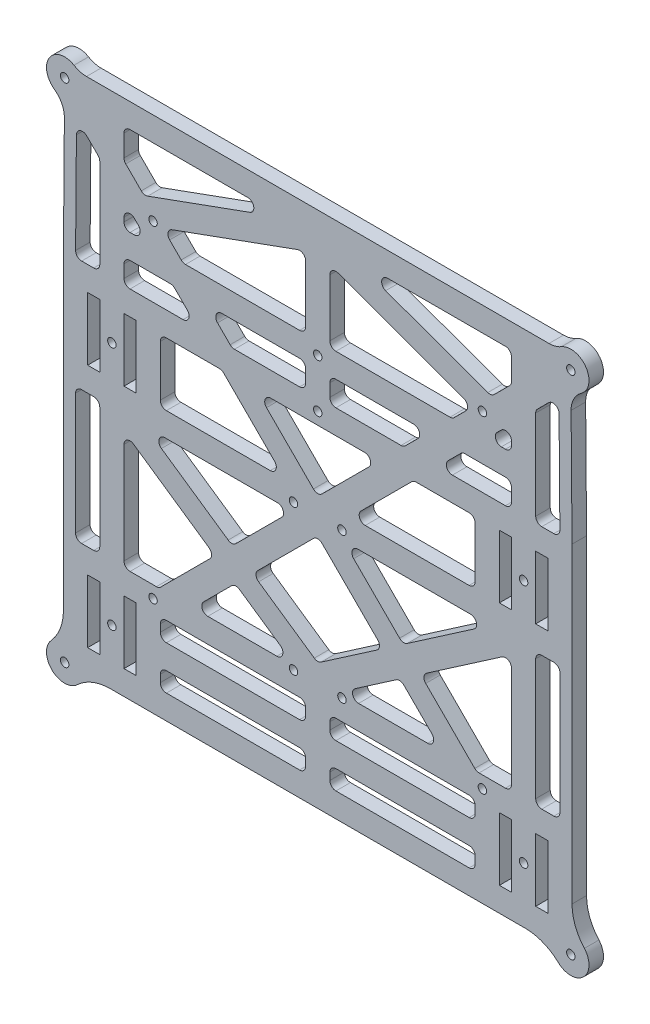
SolidWorks part; units mm, degrees
material "PMMA"
ref_plane "Płaszczyzna przednia" through (0, 0, 0) normal (0, 0, 1) x (1, 0, 0)
ref_plane "Płaszczyzna górna" through (0, 0, 0) normal (0, 1, 0) x (1, 0, 0)
ref_plane "Płaszczyzna prawa" through (0, 0, 0) normal (1, 0, 0) x (0, 0, -1)
sketch "Szkic1" plane through (0, 0, 0) normal (0, 0, 1) x (1, 0, 0)
  line L0 (-85, 104.5) -> (-85, -104.5)
  line L1 (-104.5, -104.5) -> (104.5, -104.5) construction
  line L2 (-104.5, -104.5) -> (-104.5, 104.5) construction
  line L3 (-104.5, 104.5) -> (104.5, 104.5) construction
  line L4 (104.5, -104.5) -> (104.5, 104.5) construction
  line L5 (0, 104.5) -> (0, -104.5) construction
  line L6 (-104.5, 0) -> (104.5, 0) construction
  line L7 (85, -104.5) -> (85, 104.5)
  circle A0 centre (104.5, 104.5) radius 1.75
  circle A1 centre (-104.5, 104.5) radius 1.75
  circle A2 centre (-104.5, -104.5) radius 1.75
  circle A3 centre (104.5, -104.5) radius 1.75
  point P0 (0, 0)
  dimension "D2" = 3.5
  dimension "D1" = 209
  dimension "D3" = 170
sketch "Szkic3" plane through (0, 0, 0) normal (0, 0, 1) x (1, 0, 0)
  line L6 (-80, 104.5) -> (-80, -104.5)
  line L7 (-80, -104.5) -> (-90, -104.5)
  line L8 (-90, -104.5) -> (-90, 104.5)
  line L9 (-90, 104.5) -> (-80, 104.5)
  line L10 (80, 104.5) -> (90, 104.5)
  line L11 (90, 104.5) -> (90, -104.5)
  line L12 (90, -104.5) -> (80, -104.5)
  line L13 (80, -104.5) -> (80, 104.5)
  line L15 (85, -104.5) -> (85, 104.5) construction
  line L16 (-85, 104.5) -> (-85, -104.5) construction
  dimension "D1" = 10
  dimension "D2" = 10
extrude "Dodanie-wyciągnięcie1" add sketch "Szkic3" along normal blind 6
sketch "Szkic4" plane through (0, 0, 0) normal (0, 0, 1) x (1, 0, 0)
  line L0 (-95, -94.5) -> (95, -94.5)
  line L3 (-95, -94.5) -> (-95, -104.5)
  line L4 (-95, -104.5) -> (95, -104.5)
  line L5 (95, -104.5) -> (95, -94.5)
  line L6 (-95, -68.5) -> (95, -68.5)
  line L7 (95, -68.5) -> (95, -58.5)
  line L8 (95, -58.5) -> (-95, -58.5)
  line L9 (-95, -58.5) -> (-95, -68.5)
  line L10 (-104.5, -31) -> (104.5, -31) construction
  line L12 (-95, -3.5) -> (-95, 6.5)
  line L13 (95, -3.5) -> (-95, -3.5)
  line L14 (95, 6.5) -> (95, -3.5)
  line L15 (-95, 6.5) -> (95, 6.5)
  line L16 (95, 42.5) -> (95, 32.5)
  line L17 (-95, 42.5) -> (95, 42.5)
  line L18 (-95, 32.5) -> (-95, 42.5)
  line L19 (-95, 32.5) -> (95, 32.5)
  line L20 (104.5, -104.5) -> (104.5, 104.5) construction
  line L21 (-104.5, -104.5) -> (-104.5, 104.5) construction
  line L23 (-90, -104.5) -> (-80, -104.5) construction
  line L24 (-90, 104.5) -> (-90, -104.5) construction
  line L25 (0, -31) -> (0, -14.952) construction
  line L26 (0, 104.5) -> (0, -104.5) construction
  dimension "D1" = 10
  dimension "D2" = 26
  dimension "D3" = 5
  dimension "D4" = 27.5
extrude "Dodanie-wyciągnięcie2" add sketch "Szkic4" along normal blind 6
sketch "Szkic5" plane through (0, 0, 6) normal (0, 0, 1) x (1, 0, 0)
  line L0 (-75, -68.5) -> (-75, -94.5)
  line L8 (-80, -68.5) -> (80, -68.5) construction
  line L9 (80, -94.5) -> (-80, -94.5) construction
  line L10 (-75, -94.5) -> (-65, -94.5)
  line L11 (-65, -94.5) -> (-65, -68.5)
  line L12 (-65, -68.5) -> (-75, -68.5)
  line L14 (-85, 104.5) -> (-85, -104.5) construction
  line L15 (-75, 32.5) -> (-75, 6.5)
  line L16 (-80, 32.5) -> (80, 32.5) construction
  line L17 (80, 6.5) -> (-80, 6.5) construction
  line L18 (-75, 6.5) -> (-65, 6.5)
  line L19 (-65, 6.5) -> (-65, 32.5)
  line L20 (-65, 32.5) -> (-75, 32.5)
  line L21 (0, 104.5) -> (0, -104.5) construction
  line L22 (65, 32.5) -> (75, 32.5)
  line L23 (65, 6.5) -> (65, 32.5)
  line L24 (75, 6.5) -> (65, 6.5)
  line L25 (75, 32.5) -> (75, 6.5)
  line L26 (65, -68.5) -> (75, -68.5)
  line L27 (65, -94.5) -> (65, -68.5)
  line L28 (75, -94.5) -> (65, -94.5)
  line L29 (75, -68.5) -> (75, -94.5)
  dimension "D1" = 10
  dimension "D2" = 10
extrude "Dodanie-wyciągnięcie3" add sketch "Szkic5" against normal blind 6
sketch "Szkic6" plane through (0, 0, 0) normal (0, 0, 1) x (1, 0, 0)
  line L1 (-95, 42.5) -> (-105, 42.5)
  line L2 (-95, 42.5) -> (-95, -3.5)
  line L3 (-95, -3.5) -> (-105, -3.5)
  line L4 (-105, 42.5) -> (-105, -3.5)
  line L5 (-95, -58.5) -> (-105, -58.5)
  line L6 (-95, -58.5) -> (-95, -104.5)
  line L7 (-95, -104.5) -> (-105, -104.5)
  line L8 (-105, -58.5) -> (-105, -104.5)
  line L9 (0, 104.5) -> (0, -104.5) construction
  line L10 (-104.5, 104.5) -> (104.5, 104.5) construction
  line L11 (105, -58.5) -> (105, -104.5)
  line L12 (95, -104.5) -> (105, -104.5)
  line L13 (95, -58.5) -> (95, -104.5)
  line L14 (95, -58.5) -> (105, -58.5)
  line L15 (105, 42.5) -> (105, -3.5)
  line L16 (95, -3.5) -> (105, -3.5)
  line L17 (95, 42.5) -> (95, -3.5)
  line L18 (95, 42.5) -> (105, 42.5)
  dimension "D1" = 10
extrude "Dodanie-wyciągnięcie4" add sketch "Szkic6" along normal up to surface (6 mm away) up to face at (0, -81.5, 6)
sketch "Szkic7" plane through (0, 0, 6) normal (0, 0, 1) x (1, 0, 0)
  line L0 (-104.5, -104.5) -> (104.5, -104.5) construction
  circle A0 centre (-104.5, -104.5) radius 7.5
  circle A1 centre (104.5, -104.5) radius 7.5
  dimension "D1" = 15
extrude "Dodanie-wyciągnięcie5" add sketch "Szkic7" against normal up to surface (6 mm away) contours A0 | A1 region at (-104.5, -104.5, 6) up to face at (92.5, 19.5, 0)
fillet "Zaokrąglenie1" radius 20 4 edges at (105, -97.0167, 3) (97, -104.5, 3) (-97, -104.5, 3) (-105, -97.0167, 3)
sketch "Szkic8" plane through (0, 0, 6) normal (0, 0, 1) x (1, 0, 0)
  circle A0 centre (-104.5, 104.5) radius 7.5
  circle A1 centre (104.5, 104.5) radius 7.5
  arc A2 (-110.0909, -99.5008) -> (-99.3524, -109.9545) centre (-104.5, -104.5) ccw construction
extrude "Dodanie-wyciągnięcie6" add sketch "Szkic8" against normal up to surface (6 mm away) separate body up to face at (0, -14.7636, 0)
sketch "Szkic9" plane through (0, 0, 0) normal (0, 0, 1) x (1, 0, 0)
  line L0 (-104.5, 104.5) -> (104.5, 104.5) construction
  line L1 (-104.5, 99.5) -> (104.5, 99.5)
  line L2 (-104.5, 109.5) -> (104.5, 109.5)
  line L3 (-104.5, 99.5) -> (-104.5, 109.5)
  line L4 (104.5, 99.5) -> (104.5, 109.5)
  dimension "D1" = 5
  dimension "D2" = 5
extrude "Dodanie-wyciągnięcie7" add sketch "Szkic9" along normal up to surface (6 mm away) up to face at (0, -14.7636, 6)
sketch "Szkic10" plane through (0, 0, 0) normal (0, 0, 1) x (1, 0, 0)
  line L0 (-104.5, 104.5) -> (104.5, -104.5) construction
  line L1 (104.5, 104.5) -> (-104.5, -104.5) construction
  line L2 (-80, -58.5) -> (80, -58.5) construction
  line L3 (-108.0355, 100.9645) -> (51.4289, -58.5)
  line L4 (100.9645, 108.0355) -> (-65.5711, -58.5)
  line L5 (-100.9645, 108.0355) -> (65.5711, -58.5)
  line L6 (108.0355, 100.9645) -> (-51.4289, -58.5)
  line L7 (100.9645, 108.0355) -> (-108.0355, -100.9645) construction
  line L8 (108.0355, 100.9645) -> (-100.9645, -108.0355) construction
  line L9 (-108.0355, 100.9645) -> (100.9645, -108.0355) construction
  line L10 (-100.9645, 108.0355) -> (108.0355, -100.9645) construction
  line L11 (-65.5711, -58.5) -> (-51.4289, -58.5)
  line L12 (65.5711, -58.5) -> (51.4289, -58.5)
  line L13 (-100.9645, 108.0355) -> (-108.0355, 100.9645)
  line L14 (100.9645, 108.0355) -> (108.0355, 100.9645)
  dimension "D1" = 5
  dimension "D2" = 5
extrude "Dodanie-wyciągnięcie8" add sketch "Szkic10" along normal up to surface (6 mm away) contours L5 L13 L3 L4 | L14 L4 L5 L6 | L4 L11 L6 L3 | L6 L5 L4 L3 | L12 L5 L6 L3 region at (-54.0178, 54.0178, 0) region at (0, 0, 0) region at (-31.1315, -30.9799, 0) region at (31.1315, -30.9799, 0) region at (54.0178, 54.0178, 0) up to face at (0, -10.379, 6)
sketch "Szkic11" plane through (0, 0, 0) normal (0, 0, -1) x (-1, 0, 0)
  line L0 (-65, -81.5) -> (65, -81.5) construction
  line L1 (-65, -68.5) -> (-65, -94.5) construction
  line L2 (65, -94.5) -> (65, -68.5) construction
  line L3 (80, 57.7145) -> (-80, 57.7145) construction
  line L4 (80, 42.5) -> (80, 72.9289) construction
  line L5 (-80, 72.9289) -> (-80, 42.5) construction
  line L6 (80, 62.7145) -> (-80, 62.7145)
  line L7 (80, 52.7145) -> (-80, 52.7145)
  line L8 (80, 62.7145) -> (80, 52.7145)
  line L9 (-80, 62.7145) -> (-80, 52.7145)
  line L10 (-65, -86.5) -> (65, -86.5)
  line L11 (-65, -76.5) -> (65, -76.5)
  line L12 (-65, -86.5) -> (-65, -76.5)
  line L13 (65, -86.5) -> (65, -76.5)
  dimension "D1" = 5
  dimension "D2" = 5
  dimension "D3" = 5
  dimension "D4" = 5
extrude "Dodanie-wyciągnięcie9" add sketch "Szkic11" against normal up to surface (6 mm away) up to face at (-90.8096, 98.6904, 6)
sketch "Szkic12" plane through (0, 0, 0) normal (0, 0, -1) x (-1, 0, 0)
  line L0 (-80, -3.5) -> (0, -58.5) construction
  line L1 (-51.4289, -58.5) -> (51.4289, -58.5) construction
  line L2 (0, -58.5) -> (80, -3.5) construction
  line L3 (-82.8326, -7.6202) -> (0, -64.5677)
  line L4 (0, -64.5677) -> (82.8326, -7.6202)
  line L5 (-77.1674, 0.6202) -> (0, -52.4323)
  line L6 (0, -52.4323) -> (77.1674, 0.6202)
  line L7 (-82.8326, -7.6202) -> (-77.1674, 0.6202)
  line L8 (82.8326, -7.6202) -> (77.1674, 0.6202)
  dimension "D1" = 5
  dimension "D2" = 5
extrude "Dodanie-wyciągnięcie10" add sketch "Szkic12" against normal up to surface (6 mm away) up to face at (0, -90.5, 6)
sketch "Szkic13" plane through (0, 0, 0) normal (0, 0, -1) x (-1, 0, 0)
  line L0 (-67.8217, 74.8928) -> (0, 99.5) construction
  line L1 (-80, 87.0711) -> (-55.6434, 62.7145) construction
  line L2 (80, 99.5) -> (-80, 99.5) construction
  line L3 (0, 99.5) -> (67.8217, 74.8928) construction
  line L4 (80, 87.0711) -> (55.6434, 62.7145) construction
  line L5 (-63.9188, 70.9899) -> (0, 94.1811)
  line L6 (0, 94.1811) -> (63.9188, 70.9899)
  line L7 (-71.7246, 78.7956) -> (0, 104.8189)
  line L8 (0, 104.8189) -> (71.7246, 78.7956)
  line L9 (71.7246, 78.7956) -> (63.9188, 70.9899)
  line L10 (-71.7246, 78.7956) -> (-63.9188, 70.9899)
  line L11 (-69.527, 79.593) -> (0, 104.8189) construction
  line L12 (0, 104.8189) -> (69.527, 79.593) construction
  line L13 (0, 94.1811) -> (66.1164, 70.1926) construction
  line L14 (-66.1164, 70.1926) -> (0, 94.1811) construction
  dimension "D1" = 5
  dimension "D2" = 5
extrude "Dodanie-wyciągnięcie11" add sketch "Szkic13" against normal up to surface (6 mm away) up to face at (31.4422, -52.7144, 6)
sketch "Szkic14" plane through (0, 0, 0) normal (0, 0, -1) x (-1, 0, 0)
  line L0 (-104.5, 104.5) -> (-105, 42.5) construction
  line L1 (104.5, 104.5) -> (105, 42.5) construction
  line L2 (99.5002, 104.4597) -> (100.0002, 42.4597)
  line L3 (104.5, 104.5) -> (99.5002, 104.4597)
  line L4 (105, 42.5) -> (100.0002, 42.4597)
  line L5 (104.5, 104.5) -> (105, 42.5)
  line L6 (-99.5002, 104.4597) -> (-100.0002, 42.4597)
  line L7 (-104.5, 104.5) -> (-99.5002, 104.4597)
  line L8 (-105, 42.5) -> (-100.0002, 42.4597)
  line L9 (-104.5, 104.5) -> (-105, 42.5)
  line L10 (105, -3.5) -> (105, -58.5)
  line L11 (105, -58.5) -> (100.0002, -58.5)
  line L12 (90, -58.5) -> (105, -58.5) construction
  line L13 (100.0002, -58.5) -> (100.0002, -3.5)
  line L14 (105, -3.5) -> (90, -3.5) construction
  line L15 (100.0002, -3.5) -> (105, -3.5)
  line L16 (-105, -58.5) -> (-105, -3.5)
  line L17 (-105, -3.5) -> (-100.0002, -3.5)
  line L18 (-90, -3.5) -> (-105, -3.5) construction
  line L19 (-100.0002, -3.5) -> (-100.0002, -58.5)
  line L20 (-105, -58.5) -> (-90, -58.5) construction
  line L21 (-100.0002, -58.5) -> (-105, -58.5)
  dimension "D1" = 5
  dimension "D2" = 5
extrude "Dodanie-wyciągnięcie12" add sketch "Szkic14" against normal up to surface (6 mm away) up to face at (61.5961, 91.2167, 6)
sketch "Szkic15" plane through (0, 0, 0) normal (0, 0, -1) x (-1, 0, 0)
  line L0 (0, 94.1811) -> (0, 42.5) construction
  line L1 (-35.4289, 42.5) -> (35.4289, 42.5) construction
  line L2 (-5, 94.1811) -> (-5, 42.5)
  line L3 (5, 94.1811) -> (5, 42.5)
  line L4 (-5, 94.1811) -> (5, 94.1811)
  line L5 (-5, 42.5) -> (5, 42.5)
  dimension "D1" = 5
  dimension "D2" = 5
extrude "Dodanie-wyciągnięcie13" add sketch "Szkic15" against normal up to surface (6 mm away) up to face at (95.0001, -31, 6)
sketch "Szkic16" plane through (0, 0, 0) normal (0, 0, -1) x (-1, 0, 0)
  line L0 (0, -68.5) -> (0, -94.5) construction
  line L1 (65, -68.5) -> (-65, -68.5) construction
  line L2 (-65, -94.5) -> (65, -94.5) construction
  line L3 (-5, -68.5) -> (-5, -94.5)
  line L4 (5, -68.5) -> (5, -94.5)
  line L5 (-5, -68.5) -> (5, -68.5)
  line L6 (-5, -94.5) -> (5, -94.5)
  dimension "D1" = 5
  dimension "D2" = 5
extrude "Dodanie-wyciągnięcie14" add sketch "Szkic16" against normal up to surface (6 mm away) up to face at (-32.3906, 72.1964, 6)
sketch "Szkic17" plane through (0, 0, 6) normal (0, 0, 1) x (1, 0, 0)
  line L3 (-90, 97.0711) -> (-90, 99.5)
  line L4 (-92.4289, 99.5) -> (-90, 97.0711)
  line L5 (-90, 99.5) -> (-92.4289, 99.5)
  line L6 (-90, 97.0711) -> (-90, 99.5)
  line L7 (-92.4289, 99.5) -> (-90, 97.0711)
  line L8 (-90, 99.5) -> (-92.4289, 99.5)
  line L10 (92.4289, 99.5) -> (90, 99.5)
  line L11 (90, 97.0711) -> (92.4289, 99.5)
  line L12 (90, 99.5) -> (90, 97.0711)
  line L13 (92.4289, 99.5) -> (90, 99.5)
  line L14 (90, 97.0711) -> (92.4289, 99.5)
  line L15 (90, 99.5) -> (90, 97.0711)
  dimension "D1" = 0
  dimension "D2" = 0
extrude "Dodanie-wyciągnięcie15" add sketch "Szkic17" against normal up to surface (6 mm away) up to face at (35, -72.5, 0)
fillet "Zaokrąglenie2" radius 2.5 105 edges at (90, -3.5, 3) (90, -58.5, 3) (-90, -58.5, 3) (-90, -3.5, 3) (-65, -86.5, 3) (-65, -94.5, 3) (-5, -94.5, 3) (-5, -86.5, 3) (-39.5711, 32.5, 3) (-65, 32.5, 3) (-65, 6.5, 3) (-13.5711, 6.5, 3) (-25.4289, 32.5, 3) (0, 7.0711, 3) (25.4289, 32.5, 3) (65, 6.5, 3) (65, 32.5, 3) (39.5711, 32.5, 3) (13.5711, 6.5, 3) (49.5711, 42.5, 3) (80, 42.5, 3) (80, 52.7145, 3) (59.7855, 52.7145, 3) (-45.6434, 52.7145, 3) (-35.4289, 42.5, 3) (-5, 42.5, 3) (-5, 52.7145, 3) (80, 72.9289, 3) (69.7855, 62.7145, 3) (80, 62.7145, 3) (-69.7855, 62.7145, 3) (-80, 72.9289, 3) (-80, 62.7145, 3) (-80, 42.5, 3) (-49.5711, 42.5, 3) (-59.7855, 52.7145, 3) (-80, 52.7145, 3) (-34.0721, -41.1431, 3) (-51.4289, -58.5, 3) (-8.8257, -58.5, 3) (0, -52.4323, 3) (26.8808, -33.9518, 3) (-26.8808, -33.9518, 3) (71.1743, -3.5, 3) (10.5711, -3.5, 3) (35.2613, -28.1902, 3) (42.4526, -35.3815, 3) (65.5711, -58.5, 3) (80, -58.5, 3) (80, -9.5677, 3) (-80, -58.5, 3) (-65.5711, -58.5, 3) (-42.4526, -35.3815, 3) (-80, -9.5677, 3) (-35.2613, -28.1902, 3) (-10.5711, -3.5, 3) (-71.1743, -3.5, 3) (51.4289, -58.5, 3) (34.0721, -41.1431, 3) (8.8257, -58.5, 3) (-80, 99.5, 3) (-80, 87.0711, 3) (-71.7246, 78.7956, 3) (-14.6599, 99.5, 3) (71.7246, 78.7956, 3) (80, 87.0711, 3) (80, 99.5, 3) (14.6599, 99.5, 3) (99.5964, 92.5253, 3) (90, 82.9289, 3) (90, 42.5, 3) (99.9998, 42.5, 3) (-99.9998, 42.5, 3) (-90, 42.5, 3) (-90, 82.9289, 3) (-99.5964, 92.5253, 3) (5, 62.7145, 3) (55.6434, 62.7145, 3) (63.9188, 70.9899, 3) (5, 92.367, 3) (35.4289, 42.5, 3) (45.6434, 52.7145, 3) (5, 52.7145, 3) (5, 42.5, 3) (-5, 92.367, 3) (-63.9188, 70.9899, 3) (-55.6434, 62.7145, 3) (-5, 62.7145, 3) (65, -94.5, 3) (65, -86.5, 3) (5, -86.5, 3) (5, -94.5, 3) (5, -76.5, 3) (65, -76.5, 3) (65, -68.5, 3) (5, -68.5, 3) (-65, -68.5, 3) (-5, -76.5, 3) (-5, -68.5, 3) (-65, -76.5, 3) (-100.0002, -58.5, 3) (100.0002, -58.5, 3) (100.0002, -3.5, 3) (-100.0002, -3.5, 3) (0, -7.0711, 3)
fillet "Zaokrąglenie3" radius 10 4 edges at (-98.9098, 109.5, 3) (-104.5605, 97.0002, 3) (104.5605, 97.0002, 3) (98.9098, 109.5, 3)
extrude "Wytnij-wyciągnięcie1" cut sketch "Szkic1" along normal up to next contours A1 | A0 | A3 | A2 region at (104.5, 104.5, 0) region at (-104.5, 104.5, 0) region at (-104.5, -104.5, 0) region at (104.5, -104.5, 0)
sketch "Szkic18" plane through (0, 0, 0) normal (0, 0, -1) x (-1, 0, 0)
  line L0 (-68, 71.5) -> (-68, -63.5) construction
  line L1 (-77.5, -58.5) -> (-77.5, -68.5) construction
  line L2 (-75, -68.5) -> (-80, -68.5) construction
  line L3 (-77.5, -63.5) -> (-68, -63.5) construction
  line L4 (68, -63.5) -> (-68, -63.5) construction
  line L6 (68, 71.5) -> (-68, 71.5) construction
  line L9 (0, 0) -> (0, 109.5) construction
  line L10 (-95.4861, 109.5) -> (95.4861, 109.5) construction
  circle A0 centre (-68, -63.5) radius 1.75
  circle A1 centre (-68, 71.5) radius 1.75
  circle A4 centre (68, -63.5) radius 1.75
  circle A5 centre (68, 71.5) radius 1.75
  dimension "D1" = 3.5
  dimension "D2" = 135
  dimension "D3" = 9.5
extrude "Wytnij-wyciągnięcie2" cut sketch "Szkic18" against normal up to next
sketch "Szkic19" plane through (0, 0, 0) normal (0, 0, -1) x (-1, 0, 0)
  line L0 (-90, -68.5) -> (-80, -94.5) construction
  line L1 (90, -68.5) -> (80, -94.5) construction
  line L2 (80, 32.5) -> (90, 6.5) construction
  line L3 (-80, 32.5) -> (-90, 6.5) construction
  circle A0 centre (-85, 19.5) radius 1.75
  circle A1 centre (85, 19.5) radius 1.75
  circle A2 centre (85, -81.5) radius 1.75
  circle A3 centre (-85, -81.5) radius 1.75
  dimension "D1" = 3.5
extrude "Wytnij-wyciągnięcie3" cut sketch "Szkic19" against normal up to next
sketch "Szkic20" plane through (0, 0, 6) normal (0, 0, 1) x (1, 0, 0)
  line L0 (-10, 0) -> (10, 0) construction
  line L1 (0, 0) -> (0, 37.5) construction
  line L2 (0, 37.5) -> (0, 57.5) construction
  line L3 (0, 0) -> (0, -60) construction
  line L4 (10, -60) -> (-10, -60) construction
  circle A0 centre (10, 0) radius 1.75
  circle A1 centre (-10, 0) radius 1.75
  circle A2 centre (0, 57.5) radius 1.75
  circle A3 centre (0, 37.5) radius 1.75
  circle A4 centre (10, -60) radius 1.75
  circle A5 centre (-10, -60) radius 1.75
  point P4 (0, 0)
  point P16 (0, -60)
  dimension "D2" = 3.5
  dimension "D5" = 60
  dimension "D1" = 20
  dimension "D3" = 37.5
  dimension "D4" = 20
extrude "Wytnij-wyciągnięcie4" cut sketch "Szkic20" against normal up to next
equation "\"D2@Szkic3\"=\"D1@Szkic3\""
